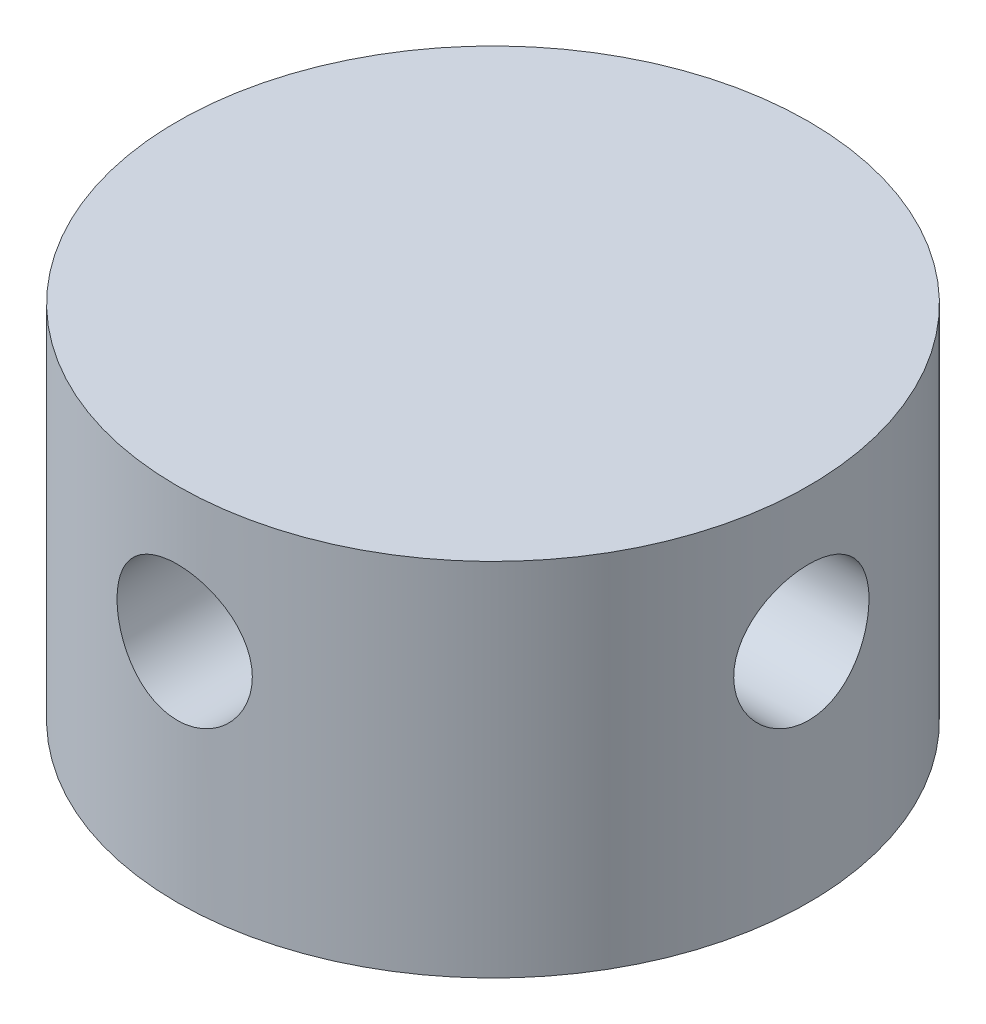
SolidWorks part; units mm, degrees
ref_plane "Front Plane" through (0, 0, 0) normal (0, 0, 1) x (1, 0, 0)
ref_plane "Top Plane" through (0, 0, 0) normal (0, 1, 0) x (1, 0, 0)
ref_plane "Right Plane" through (0, 0, 0) normal (1, 0, 0) x (0, 0, -1)
sketch "Sketch1" plane through (0, 0, 0) normal (0, 1, 0) x (1, 0, 0)
  circle A0 centre (0, 0) radius 14
  dimension "D1" = 28
extrude "Boss-Extrude1" add sketch "Sketch1" along normal blind 16
ref_plane "Plane1" through (14, 0, 0) normal (1, 0, 0) x (0, 0, -1)
ref_axis "Axis1" through (0, 16, 0) along (0, -1, 0)
sketch "Sketch2" plane through (14, 0, 0) normal (1, 0, 0) x (0, 0, -1)
  line L0 (0, 19.9907) -> (0, 0) construction
  line L1 (0, 16) -> (0, 0) construction
  circle A0 centre (0, 9.9954) radius 3
  dimension "D1" = 6
extrude "Cut-Extrude1" cut sketch "Sketch2" against normal blind 5
pattern_circular "CirPattern1" count 4 over 360 about axis through (0, 16, 0) along (0, -1, 0) of "Cut-Extrude1"
